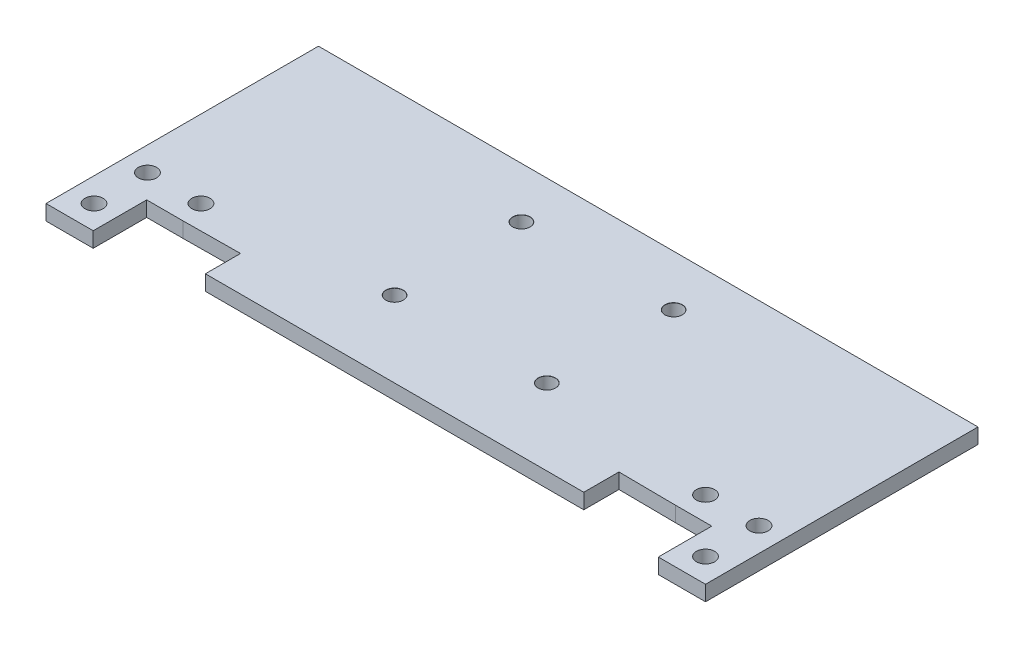
SolidWorks part; units mm, degrees
ref_plane "Front Plane" through (0, 0, 0) normal (0, 0, 1) x (1, 0, 0)
ref_plane "Top Plane" through (0, 0, 0) normal (0, 1, 0) x (1, 0, 0)
ref_plane "Right Plane" through (0, 0, 0) normal (1, 0, 0) x (0, 0, -1)
sketch "Sketch1" plane through (0, 0, 0) normal (1, 0, 0) x (0, 0, -1)
  line L2 (3.71, 3) -> (53.71, 3)
  line L6 (3.71, 0) -> (53.71, 0)
  line L7 (53.71, 0) -> (53.71, 3)
  line L8 (3.71, 3) -> (3.71, 0)
  dimension "D1" = 3.71
  dimension "D3" = 50
  dimension "D6" = 3
extrude "Boss-Extrude1" add sketch "Sketch1" along normal blind 130
hole_wizard "M3 Clearance Hole2" positions "Sketch5" profile "Sketch6" hole size "M3" standard "ANSI Metric" end condition through all
sketch "Sketch5" plane through (0, 3, 0) normal (0, 1, 0) x (1, 0, 0)
  line L0 (65, 53.71) -> (65, 43.71) construction
  line L1 (130, 53.71) -> (0, 53.71) construction
  line L3 (50, 43.71) -> (80, 43.71) construction
  line L4 (80, 43.71) -> (80, 18.71) construction
  line L5 (80, 18.71) -> (50, 18.71) construction
  line L6 (50, 18.71) -> (50, 43.71) construction
  line L7 (130, 3.71) -> (0, 3.71) construction
  point P9 (50, 43.71)
  point P11 (80, 43.71)
  point P13 (50, 18.71)
  point P15 (80, 18.71)
  point P25 (65, 43.71)
  dimension "D1" = 30
  dimension "D2" = 25
  dimension "D3" = 10
  dimension "D4" = 15
sketch "Sketch6" plane through (80, 3, -18.71) normal (1, 0, 0) x (0, 0, 1)
  line L0 (0, 0) -> (0, 3)
  line L1 (0, 3) -> (1.7, 3)
  line L2 (1.7, 3) -> (1.7, 0.025)
  line L3 (1.7, 0.025) -> (1.725, 0)
  line L5 (1.725, 0) -> (0, 0)
  line L6 (-1.7, 0.025) -> (-1.725, 0) construction
  line L11 (0, -6.35) -> (0, 107.95) construction
  dimension "Thru Hole Dia." = 3.4
  dimension "Thru Hole Depth" = 3
  dimension "Near C'Sink Dia." = 3.45
  dimension "Near C'Sink Angle" = 90
sketch "Sketch7" plane through (0, 0, 0) normal (0, -1, 0) x (1, 0, 0)
  line L0 (130, -3.71) -> (0, -3.71) construction
  line L1 (130, -3.71) -> (0, -3.71)
  line L2 (108.1956, -3.71) -> (108.1956, 0.0001)
  line L3 (108.1956, 0.0001) -> (130, 0.0001)
  line L4 (130, 13.0001) -> (130, -19.9999) construction
  line L5 (130, 0.0001) -> (130, -3.71)
  line L6 (125.2699, -4.73) -> (130, -4.73) construction
  line L7 (130, -3.71) -> (130, -53.71) construction
  line L8 (119.0978, 0.0001) -> (119.0978, -4.73) construction
  line L9 (120.4956, -10.3397) -> (120.4956, 4.3493) construction
  line L10 (120.4956, -10.3397) -> (120.4956, 4.3493) construction
  line L11 (65, -3.71) -> (65, -53.71) construction
  line L12 (130, -53.71) -> (0, -53.71) construction
  line L13 (0, 0.0001) -> (0, -3.71)
  line L14 (21.8044, 0.0001) -> (0, 0.0001)
  line L15 (21.8044, -3.71) -> (21.8044, 0.0001)
  circle A0 centre (125.2699, -4.73) radius 1.8 construction
  circle A1 centre (125.2699, -4.73) radius 1.8 construction
  line M17 (130, -3.71) -> (0, -3.71)
  dimension "D1" = 12.3
extrude "Boss-Extrude2" add sketch "Sketch7" against normal up to surface (3 mm away) contours L5 L3 L2 M17 | L15 L14 L13 M17 region at (10.9022, 0, -1.8549) region at (119.0978, 0, -1.8549) up to face at (50, 3, -41.985)
sketch "Sketch9" plane through (0, 3, 0) normal (0, 1, 0) x (1, 0, 0)
  line L0 (120.4956, 10.3397) -> (113.4956, 10.3397) construction
  line L1 (120.4956, 10.3397) -> (120.4956, -4.3493) construction
  line L2 (120.4956, 10.3397) -> (113.4956, 10.3397)
  line L3 (120.4956, 10.3397) -> (120.4956, -4.3493)
  line L4 (102.4956, 0.9897) -> (102.4956, 10.4376) construction
  line L5 (102.4956, 0.9897) -> (102.4956, 10.4376)
  line L6 (113.4956, 10.3397) -> (102.4956, 10.4376)
  line L7 (102.4956, 0.9897) -> (120.4956, -4.3493)
  line L8 (102.2956, 0.8404) -> (102.2956, 10.6394)
  line L9 (113.4965, 10.5397) -> (102.2956, 10.6394)
  line L10 (120.6956, 10.5397) -> (113.4965, 10.5397)
  line L11 (120.6956, 10.5397) -> (120.6956, -4.6173)
  line L12 (102.2956, 0.8404) -> (120.6956, -4.6173)
  line L13 (108.1956, 3.71) -> (21.8044, 3.71) construction
  line L14 (130, 53.71) -> (0, 53.71) construction
  line L15 (108.1956, 3.71) -> (21.8044, 3.71) construction
  line L16 (130, 53.71) -> (0, 53.71) construction
  line L17 (65, 53.71) -> (65, 3.71) construction
  line L18 (9.3044, 10.5397) -> (9.3044, -4.6173)
  line L19 (9.3044, 10.5397) -> (16.5035, 10.5397)
  line L20 (16.5035, 10.5397) -> (27.7044, 10.6394)
  line L21 (27.7044, 0.8404) -> (27.7044, 10.6394)
  line L22 (27.7044, 0.8404) -> (9.3044, -4.6173)
  line M8 (21.8044, -0.0001) -> (21.8044, 3.71)
  line M9 (21.8044, 3.71) -> (108.1956, 3.71)
  line M10 (108.1956, 3.71) -> (108.1956, -0.0001)
  dimension "D1" = 0.2
extrude "Cut-Extrude1" cut sketch "Sketch9" against normal through all contours L2 L6 L5 L3 M9 | L5 L7 L3 M9 | L8 L12 L11 L3 L7 L5 M10 M9 | L11 L10 L9 L8 L5 L6 L2 L3 M9 | L21 L20 L19 L18 M9 | L22 L21 L18 M9 M8 region at (112.147, 3, -4.2464) region at (102.3195, 3, -7.1747) region at (17.846, 3, -4.2412)
sketch "Sketch10" plane through (0, 3, 0) normal (0, 1, 0) x (1, 0, 0)
  point P0 (125.2699, 4.73)
  point P3 (125.2699, 15.2698)
  point P6 (114.7301, 15.2698)
hole_wizard "M3 Clearance Hole3" positions "Sketch10" profile "Sketch11" hole size "M3" standard "ANSI Metric" end condition through all
sketch "Sketch11" plane through (125.2699, 3, -4.73) normal (1, 0, 0) x (0, 0, 1)
  line L0 (0, 0) -> (0, 3)
  line L1 (0, 3) -> (1.8, 3)
  line L2 (1.8, 3) -> (1.8, 0)
  line L5 (1.8, 0) -> (0, 0)
  line L11 (0, -6.35) -> (0, 107.95) construction
  dimension "Thru Hole Dia." = 3.6
  dimension "Thru Hole Depth" = 3
ref_plane "Plane1" through (65, 0, 0) normal (1, 0, 0) x (0, 0, -1)
mirror "Mirror1" about plane through (65, 0, 0) normal (1, 0, 0) of "M3 Clearance Hole3"
